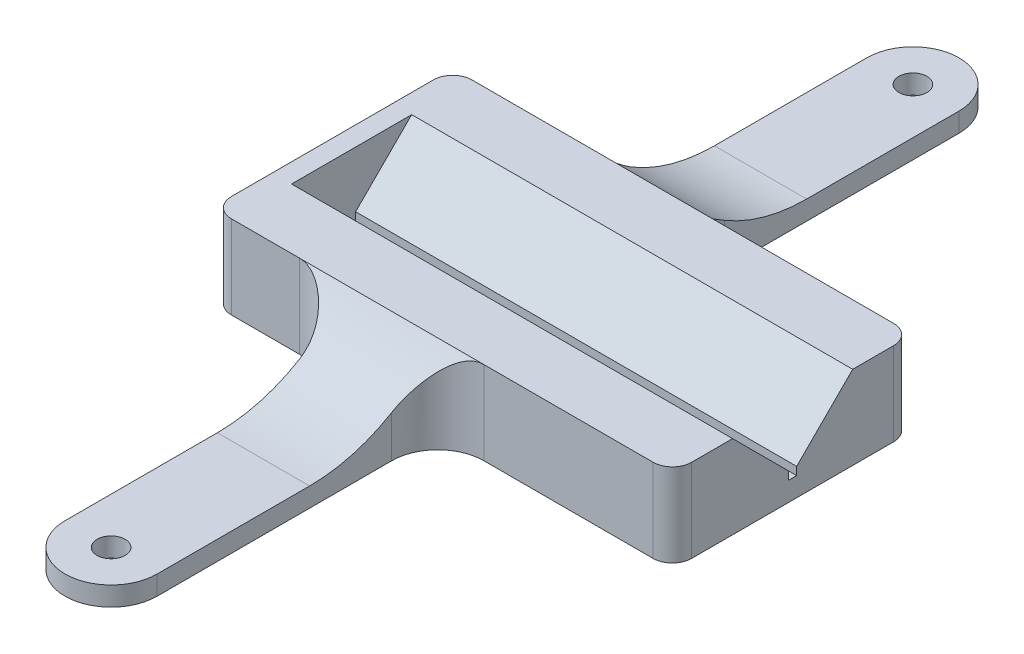
SolidWorks part; units mm, degrees
ref_plane "Front Plane" through (0, 0, 0) normal (0, 0, 1) x (1, 0, 0)
ref_plane "Top Plane" through (0, 0, 0) normal (0, 1, 0) x (1, 0, 0)
ref_plane "Right Plane" through (0, 0, 0) normal (1, 0, 0) x (0, 0, -1)
sketch "Sketch1" plane through (0, 0, 0) normal (0, 1, 0) x (1, 0, 0)
  line L0 (-50, 50) -> (-50, -50) construction
  line L1 (-50, 0) -> (50, 0) construction
  line L2 (-44.25, 50) -> (-44.25, 20.75)
  line L3 (-38.5, 15) -> (-15, 15)
  line L4 (-15, 15) -> (-15, -15)
  line L5 (-15, -15) -> (-38.5, -15)
  line L6 (-44.25, -20.75) -> (-44.25, -50)
  line L7 (-55.75, 50) -> (-55.75, 20.75)
  line L8 (-61.5, 15) -> (-72.4, 15)
  line L9 (-72.4, 15) -> (-72.4, -15)
  line L10 (-72.4, -15) -> (-61.5, -15)
  line L11 (-55.75, -20.75) -> (-55.75, -50)
  line L12 (-70, 15) -> (-70, -15) construction
  circle A0 centre (-50, 50) radius 1.75
  circle A1 centre (-50, -50) radius 1.75
  arc A2 (-44.25, 50) -> (-55.75, 50) centre (-50, 50) ccw
  arc A3 (-55.75, -50) -> (-44.25, -50) centre (-50, -50) ccw
  arc A4 (-38.5, -15) -> (-44.25, -20.75) centre (-38.5, -20.75) ccw
  arc A5 (-44.25, 20.75) -> (-38.5, 15) centre (-38.5, 20.75) ccw
  arc A6 (-61.5, -15) -> (-55.75, -20.75) centre (-61.5, -20.75) cw
  arc A7 (-61.5, 15) -> (-55.75, 20.75) centre (-61.5, 20.75) ccw
  point P25 (-55.75, -15)
  point P30 (0, 0)
  dimension "D2" = 3.5
  dimension "D3" = 30
  dimension "D4" = 4
  dimension "D6" = 70
  dimension "D1" = 100
  dimension "D5" = 15
  dimension "D7" = 2.4
extrude "Boss-Extrude1" add sketch "Sketch1" along normal blind 2.4
sketch "Sketch2" plane through (-15, 0, 0) normal (1, 0, 0) x (0, 0, -1)
  line L0 (-15, 0) -> (-15, 10.3901)
  line L1 (-15, 10.3901) -> (-7.4901, 10.3901)
  line L2 (-7.4901, 10.3901) -> (-0.5, 3.4)
  line L4 (0.5, 3.4) -> (7.4901, 10.3901)
  line L5 (7.4901, 10.3901) -> (15, 10.3901)
  line L6 (15, 10.3901) -> (15, 0)
  line L7 (15, 0) -> (-15, 0)
  line L8 (-0.5, 3.4) -> (-0.5, 2.4)
  line L9 (-0.5, 2.4) -> (0.5, 2.4)
  line L10 (0.5, 2.4) -> (0.5, 3.4)
  line L11 (-15, 2.4) -> (15, 2.4) construction
  circle A0 centre (0, 2.9) radius 0.5 construction
  circle A1 centre (0, 11.8803) radius 6.35 construction
  point P15 (-4.4901, 7.3901)
  dimension "D2" = 1
  dimension "D3" = 12.7
  dimension "D1" = 90
  dimension "D4" = 3
extrude "Boss-Extrude2" add sketch "Sketch2" against normal up to surface (57.4 mm away) up to face at (-72.4, 1.2, 0)
sketch "Sketch3" plane through (-72.4, 0, 0) normal (-1, 0, 0) x (0, 0, 1)
  line L1 (-15, 10.3901) -> (15, 10.3901)
  line L2 (-15, 10.3901) -> (-15, 0)
  line L3 (-15, 0) -> (15, 0)
  line L4 (15, 10.3901) -> (15, 0)
extrude "Boss-Extrude3" add sketch "Sketch3" against normal up to vertex (2.4 mm away) up to point (-70, 0, 15)
fillet "Fillet1" radius 20 2 edges at (-50, 2.4, -15) (-50, 2.4, 15)
fillet "Fillet2" radius 2.4 4 edges at (-15, 5.1951, 15) (-15, 5.1951, -15) (-72.4, 5.1951, -15) (-72.4, 5.1951, 15)
